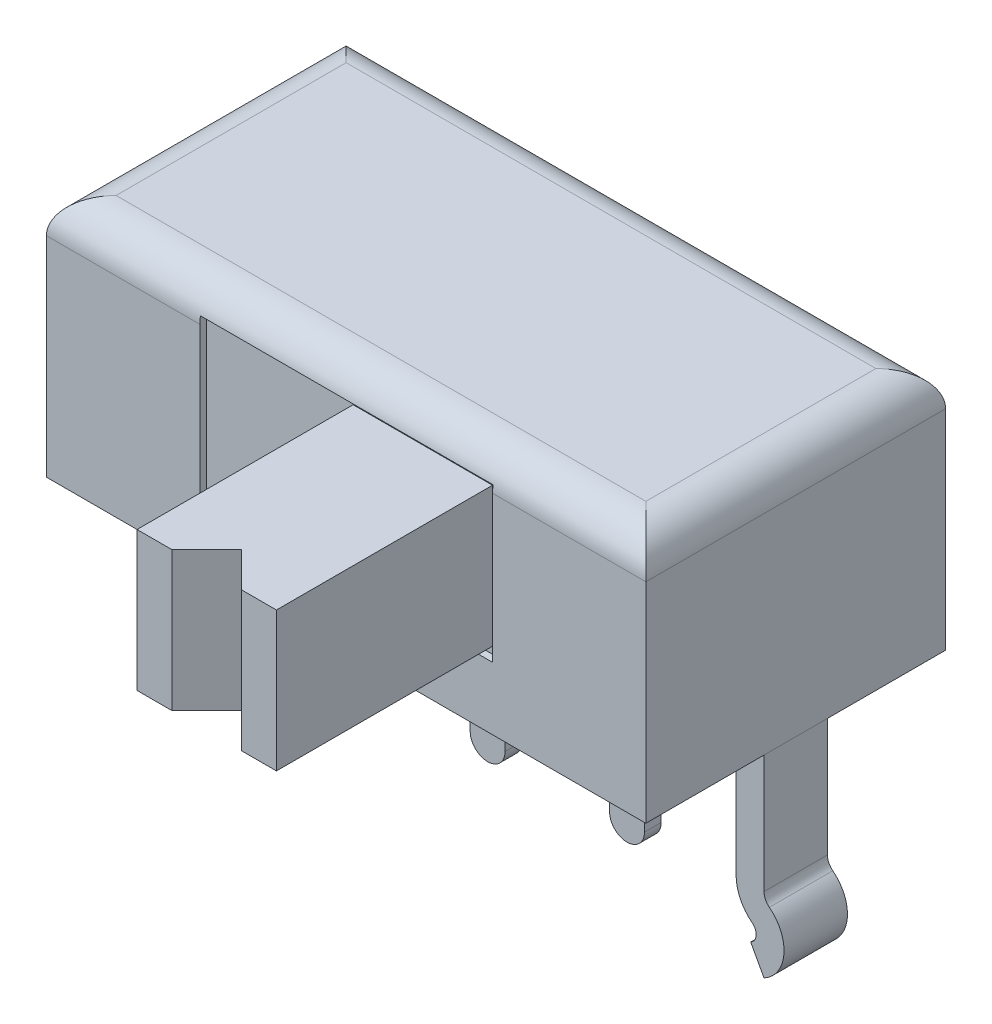
SolidWorks part; units mm, degrees
ref_plane "Front Plane" through (0, 0, 0) normal (0, 0, 1) x (1, 0, 0)
ref_plane "Top Plane" through (0, 0, 0) normal (0, 1, 0) x (1, 0, 0)
ref_plane "Right Plane" through (0, 0, 0) normal (1, 0, 0) x (0, 0, -1)
sketch "Sketch1" plane through (0, 0, 0) normal (0, 1, 0) x (1, 0, 0)
  line L1 (4.3, -2.15) -> (-4.3, -2.15)
  line L2 (4.3, -2.15) -> (4.3, 2.15)
  line L3 (4.3, 2.15) -> (-4.3, 2.15)
  line L4 (-4.3, -2.15) -> (-4.3, 2.15)
  line L5 (4.3, -2.15) -> (-4.3, 2.15) construction
  line L6 (4.3, 2.15) -> (-4.3, -2.15) construction
  point P0 (0, 0)
  dimension "D1" = 8.6
  dimension "D2" = 4.3
extrude "Boss-Extrude1" add sketch "Sketch1" along normal blind 3.5
sketch "Sketch2" plane through (0, 0, 0) normal (0, 0, 1) x (1, 0, 0)
  line L0 (3.9, 0) -> (3.9, -1.6963)
  line L1 (4.1091, -2.4185) -> (4.3, -2.77)
  line L2 (4.3, -1.6963) -> (4.3, 0)
  line L3 (4.3, 0) -> (3.9, 0)
  line L4 (-4.3, -2.77) -> (-4.1091, -2.4185)
  line L5 (-3.9, -1.6963) -> (-3.9, 0)
  line L6 (-3.9, 0) -> (-4.3, 0)
  line L7 (-4.3, 0) -> (-4.3, -1.6963)
  arc A0 (3.9, -1.6963) -> (4.13, -2.1686) centre (4.5, -1.6963) ccw
  arc A1 (4.1091, -2.4185) -> (4.13, -2.1686) centre (4.0375, -2.2867) ccw
  arc A2 (4.3, -2.77) -> (4.3767, -1.8537) centre (4.0375, -2.2867) ccw
  arc A3 (4.3, -1.6963) -> (4.3767, -1.8537) centre (4.5, -1.6963) ccw
  arc A4 (-4.3767, -1.8537) -> (-4.3, -1.6963) centre (-4.5, -1.6963) ccw
  arc A5 (-4.3767, -1.8537) -> (-4.3, -2.77) centre (-4.0375, -2.2867) ccw
  arc A6 (-4.13, -2.1686) -> (-4.1091, -2.4185) centre (-4.0375, -2.2867) ccw
  arc A7 (-4.13, -2.1686) -> (-3.9, -1.6963) centre (-4.5, -1.6963) ccw
  point P24 (-4.3, 0)
extrude "Boss-Extrude2" add sketch "Sketch2" along normal mid plane 0.91 separate body
sketch "Sketch3" plane through (0, 0, 0) normal (0, 0, 1) x (1, 0, 0)
  line L0 (2.25, -2.15) -> (2.25, 0)
  line L1 (2.25, 0) -> (1.75, 0)
  line L2 (1.75, 0) -> (1.75, -2.15)
  line L3 (0.25, -2.15) -> (0.25, 0)
  line L4 (0.25, 0) -> (-0.25, 0)
  line L5 (-0.25, 0) -> (-0.25, -2.15)
  line L6 (-1.75, -2.15) -> (-1.75, 0)
  line L7 (-1.75, 0) -> (-2.25, 0)
  line L8 (-2.25, 0) -> (-2.25, -2.15)
  arc A0 (1.75, -2.15) -> (2.25, -2.15) centre (2, -2.15) ccw
  arc A1 (-0.25, -2.15) -> (0.25, -2.15) centre (0, -2.15) ccw
  arc A2 (-2.25, -2.15) -> (-1.75, -2.15) centre (-2, -2.15) ccw
extrude "Boss-Extrude3" add sketch "Sketch3" along normal mid plane 0.24 separate body
sketch "Sketch4" plane through (0, 0, 2.15) normal (0, 0, 1) x (1, 0, 0)
  line L11 (2.1, 0.9) -> (2.1, 3.1)
  line L12 (2.1, 3.1) -> (1.5, 3.1)
  line L13 (1.5, 3.1) -> (1, 3.1)
  line L14 (1, 3.1) -> (0.5, 3.1)
  line L18 (0.5, 0.9) -> (1, 0.9)
  line L19 (1, 0.9) -> (1.5, 0.9)
  line L20 (1.5, 0.9) -> (2.1, 0.9)
  line L24 (-2.1, 3.1) -> (-1.5, 3.1)
  line L25 (-1.5, 3.1) -> (-1, 3.1)
  line L26 (-1, 3.1) -> (-0.5, 3.1)
  line L27 (-0.5, 0.9) -> (-1, 0.9)
  line L28 (-1, 0.9) -> (-1.5, 0.9)
  line L29 (-1.5, 0.9) -> (-2.1, 0.9)
  line L30 (-2.1, 0.9) -> (-2.1, 3.1)
  line L31 (-0.5, 3.1) -> (0.5, 3.1)
  line L32 (-0.5, 0.9) -> (0.5, 0.9)
extrude "Cut-Extrude1" cut sketch "Sketch4" against normal blind 0.1
sketch "Sketch5" plane through (0, 0, 2.05) normal (0, 0, 1) x (1, 0, 0)
  line L0 (0.5, 3) -> (0, 3)
  line L1 (0, 3) -> (0, 1)
  line L2 (0, 1) -> (0.5, 1)
  line L3 (1, 3) -> (0.5, 3)
  line L4 (0.5, 1) -> (1, 1)
  line L5 (1.5, 3) -> (1, 3)
  line L6 (1, 1) -> (1.5, 1)
  line L7 (2, 1) -> (2, 3)
  line L8 (2, 3) -> (1.5, 3)
  line L9 (1.5, 1) -> (2, 1)
  line L10 (0, 0) -> (0, 0.8923) construction
extrude "Boss-Extrude4" add sketch "Sketch5" along normal blind 3.1 separate body
sketch "Sketch6" plane through (0, 3, 0) normal (0, 1, 0) x (1, 0, 0)
  line L0 (0.5, -5.15) -> (1.5, -5.15)
  line L1 (1, -4.65) -> (1.5, -5.15)
  line L2 (0.5, -5.15) -> (1, -4.65)
extrude "Cut-Extrude2" cut sketch "Sketch6" against normal through all
fillet "Fillet1" radius 0.5 4 edges at (-4.3, 3.5, 0) (0, 3.5, -2.15) (4.3, 3.5, 0) (0, 3.5, 2.15)
